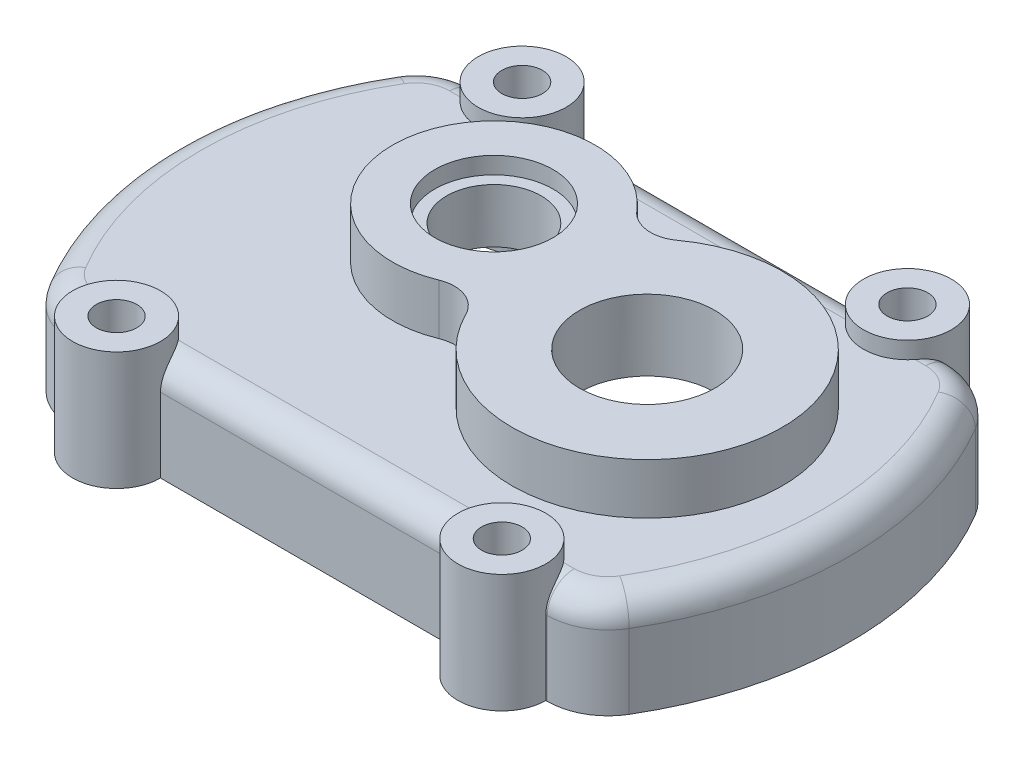
SolidWorks part; units mm, degrees
ref_plane "Front Plane" through (0, 0, 0) normal (0, 0, 1) x (1, 0, 0)
ref_plane "Top Plane" through (0, 0, 0) normal (0, 1, 0) x (1, 0, 0)
ref_plane "Right Plane" through (0, 0, 0) normal (1, 0, 0) x (0, 0, -1)
sketch "Sketch1" plane through (0, 0, 0) normal (0, 1, 0) x (1, 0, 0)
  line L1 (-70.4273, 60) -> (70.4273, 60)
  line L3 (-70.4273, -60) -> (70.4273, -60)
  line L5 (-85.7493, 51.4496) -> (85.7493, -51.4496) construction
  line L6 (-85.7493, -51.4496) -> (85.7493, 51.4496) construction
  arc A0 (-85.8869, 51.2195) -> (-85.8869, -51.2195) centre (0, 0) ccw
  arc A1 (85.8869, -51.2195) -> (85.8869, 51.2195) centre (0, 0) ccw
  arc A2 (70.4273, 60) -> (85.8869, 51.2195) centre (70.4273, 42) cw
  arc A3 (85.8869, -51.2195) -> (70.4273, -60) centre (70.4273, -42) cw
  arc A4 (-70.4273, -60) -> (-85.8869, -51.2195) centre (-70.4273, -42) cw
  arc A5 (-85.8869, 51.2195) -> (-70.4273, 60) centre (-70.4273, 42) cw
  point P0 (0, 0)
  dimension "D1" = 18
extrude "Boss-Extrude1" add sketch "Sketch1" along normal blind 30
shell "Shell1" thickness 6 removed face at (0, 0, 0)
sketch "Sketch2" plane through (0, 30, 0) normal (0, 1, 0) x (1, 0, 0)
  line L0 (0, 0) -> (134.689, 0) construction
  line L1 (134.689, 0) -> (-125.9592, 0) construction
  line L2 (0, 0) -> (0, 73.4242) construction
  line L3 (0, 73.4242) -> (0, -67.8122) construction
  line L4 (57, 0) -> (57, 73.4242) construction
  line L5 (41.4668, 60) -> (68.2799, 60) construction
  line L6 (70.4273, 60) -> (-70.4273, 60) construction
  circle A0 centre (57, 60) radius 13
  circle A1 centre (57, 60) radius 6
  circle A2 centre (-57, 60) radius 6
  circle A3 centre (-57, 60) radius 13
  circle A4 centre (-57, -60) radius 13
  circle A5 centre (-57, -60) radius 6
  circle A6 centre (57, -60) radius 6
  circle A7 centre (57, -60) radius 13
  dimension "D1" = 57
extrude "Boss-Extrude3" add sketch "Sketch2" along normal blind 5 and the other way blind 30
sketch "Sketch5" plane through (0, 35, 0) normal (0, 1, 0) x (1, 0, 0)
  circle A0 centre (-57, 60) radius 6 construction
  circle A1 centre (-57, -60) radius 6 construction
  circle A2 centre (57, -60) radius 6 construction
  circle A3 centre (57, 60) radius 6 construction
  circle A4 centre (-57, 60) radius 6
  circle A5 centre (-57, -60) radius 6
  circle A6 centre (57, -60) radius 6
  circle A7 centre (57, 60) radius 6
extrude "Cut-Extrude1" cut sketch "Sketch5" against normal blind 35
fillet "Fillet1" radius 8 12 edges at (70.2136, 30, 60) (70.2136, 30, -60) (-70.2136, 30, -60) (-70.2136, 30, 60) (79.3168, 30, 57.6517) (79.3168, 30, -57.6517) (-79.3168, 30, 57.6517) (-79.3168, 30, -57.6517) (100, 30, 0) (0, 30, 60) (-100, 30, 0) (0, 30, -60)
sketch "Sketch6" plane through (0, 30, 0) normal (0, 1, 0) x (1, 0, 0)
  line L0 (0, 0) -> (141.86, 0) construction
  line L1 (141.86, 0) -> (-122.5296, 0) construction
  line L2 (-122.5296, 0) -> (0, 0) construction
  line L3 (0, 0) -> (0, 69.9947) construction
  line L4 (0, 69.9947) -> (0, -68.4358) construction
  line L5 (0, 15) -> (-122.5296, 15) construction
  line L6 (40, 0) -> (40, 69.9947)
  line L7 (141.86, 15) -> (-122.5296, 15) construction
  line L9 (-33.0487, 15) -> (-13.0948, 15) construction
  line L10 (-20, 24.7865) -> (-20, 4.5208) construction
  line L11 (-20, 4.5208) -> (-20, 14.6537) construction
  line L13 (-20, 14.6537) -> (-20, 15)
  arc A0 (4.2072, -17.8572) -> (16.4682, 32.3459) centre (40, 0) ccw
  arc A1 (2.939, 33.9877) -> (-8.5557, -13.0777) centre (-20, 14.6537) ccw
  arc A2 (4.2072, -17.8572) -> (-8.5557, -13.0777) centre (-4.7409, -22.3215) ccw
  arc A3 (16.4682, 32.3459) -> (2.939, 33.9877) centre (10.5853, 40.4323) cw
  point P12 (-20, 0)
  point P13 (-20, 69.9947)
  dimension "D3" = 10
  dimension "D1" = 15
  dimension "D2" = 40
extrude "Boss-Extrude4" add sketch "Sketch6" along normal blind 15 contours A0 A3 A1 A2 region at (18.6093, 30, -5.2242)
sketch "Sketch7" plane through (0, 45, 0) normal (0, 1, 0) x (1, 0, 0)
  circle A0 centre (40, 0) radius 20
  circle A1 centre (-20, 14.6537) radius 14
extrude "Cut-Extrude3" cut sketch "Sketch7" against normal blind 40
sketch "Sketch8" plane through (0, 45, 0) normal (0, 1, 0) x (1, 0, 0)
  circle A0 centre (-20, 14.6537) radius 17.5
extrude "Cut-Extrude4" cut sketch "Sketch8" against normal blind 5
